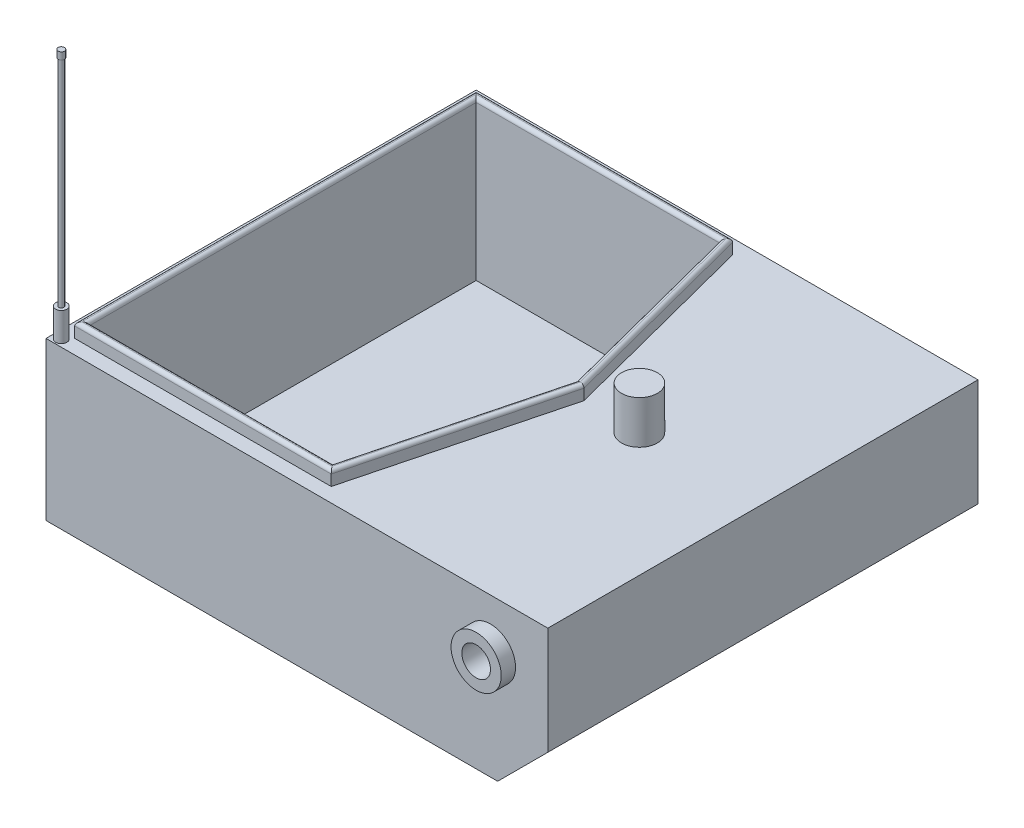
SolidWorks part; units mm, degrees
ref_plane "Front Plane" through (0, 0, 0) normal (0, 0, 1) x (1, 0, 0)
ref_plane "Top Plane" through (0, 0, 0) normal (0, 1, 0) x (1, 0, 0)
ref_plane "Right Plane" through (0, 0, 0) normal (1, 0, 0) x (0, 0, -1)
sketch "Sketch1" plane through (0, 0, 0) normal (0, 0, 1) x (1, 0, 0)
  line L0 (280, -110) -> (350, -40)
  line L1 (-350, -110) -> (280, -110)
  line L2 (-350, -110) -> (-350, 110)
  line L3 (-350, 110) -> (350, 110)
  line L4 (350, -40) -> (350, 110)
  line L5 (-350, -110) -> (350, 110) construction
  line L6 (-350, 110) -> (350, -110) construction
  point P0 (0, 0)
  dimension "D1" = 700
  dimension "D2" = 220
extrude "Boss-Extrude1" add sketch "Sketch1" along normal blind 600
sketch "Sketch2" plane through (0, 110, 0) normal (0, 1, 0) x (1, 0, 0)
  line L0 (20.0986, -30) -> (90.0986, -300)
  line L1 (-320, -30) -> (20.0986, -30)
  line L2 (-320, -30) -> (-320, -570)
  line L3 (-320, -570) -> (20.0986, -570)
  line L5 (90.0986, -300) -> (20.0986, -570)
  line L6 (350, 0) -> (-350, 0) construction
  line L7 (350, -600) -> (-350, -600) construction
  line L8 (-350, -600) -> (-350, 0) construction
  dimension "D1" = 30
  dimension "D2" = 30
  dimension "D3" = 30
extrude "Cut-Extrude1" cut sketch "Sketch2" against normal blind 200
sketch "Sketch3" plane through (0, 110, 0) normal (0, 1, 0) x (1, 0, 0)
  line L0 (-330, -20) -> (-330, -580)
  line L1 (-330, -580) -> (27.8367, -580)
  line L2 (27.8367, -580) -> (100.4292, -300)
  line L3 (100.4292, -300) -> (27.8367, -20)
  line L4 (27.8367, -20) -> (-330, -20)
  line L5 (-320, -30) -> (-320, -570)
  line L6 (-320, -570) -> (20.0986, -570)
  line L7 (20.0986, -570) -> (90.0986, -300)
  line L8 (90.0986, -300) -> (20.0986, -30)
  line L9 (20.0986, -30) -> (-320, -30)
  line L10 (-320, -30) -> (-320, -570)
  line L11 (-320, -570) -> (20.0986, -570)
  line L12 (20.0986, -570) -> (90.0986, -300)
  line L13 (90.0986, -300) -> (20.0986, -30)
  line L14 (20.0986, -30) -> (-320, -30)
  dimension "D1" = 0
  dimension "D2" = 10
extrude "Boss-Extrude2" add sketch "Sketch3" along normal blind 20
fillet "Fillet1" radius 5 10 edges at (-149.9507, 130, 570) (55.0986, 130, 435) (55.0986, 130, 165) (-149.9507, 130, 30) (-320, 130, 300) (64.133, 130, 160) (64.133, 130, 440) (-151.0817, 130, 580) (-330, 130, 300) (-151.0817, 130, 20)
sketch "Sketch4" plane through (0, 0, 600) normal (0, 0, 1) x (1, 0, 0)
  line L0 (350, 110) -> (-350, 110) construction
  line L1 (350, -40) -> (350, 110) construction
  circle A0 centre (270, 40) radius 35
  dimension "D3" = 70
  dimension "D1" = 70
  dimension "D2" = 80
extrude "Boss-Extrude3" add sketch "Sketch4" along normal blind 20
sketch "Sketch5" plane through (0, 0, 0) normal (0, 0, -1) x (-1, 0, 0)
  line L0 (-350, 110) -> (350, 110) construction
  line L1 (-350, -40) -> (-350, 110) construction
  circle A0 centre (-270, 40) radius 35
  dimension "D1" = 70
  dimension "D2" = 70
  dimension "D3" = 80
extrude "Boss-Extrude4" add sketch "Sketch5" along normal blind 20
sketch "Sketch6" plane through (0, 0, 620) normal (0, 0, 1) x (1, 0, 0)
  circle A0 centre (270, 40) radius 10
  dimension "D1" = 20
extrude "Cut-Extrude2" cut sketch "Sketch6" against normal through all
sketch "Sketch7" plane through (0, 110, 0) normal (0, 1, 0) x (1, 0, 0)
  circle A0 centre (177.7521, -300) radius 25
  dimension "D1" = 50
extrude "Boss-Extrude5" add sketch "Sketch7" along normal blind 60
sketch "Sketch9" plane through (0, 0, 620) normal (0, 0, 1) x (1, 0, 0)
  circle A0 centre (270, 40) radius 20
  dimension "D1" = 40
extrude "Cut-Extrude3" cut sketch "Sketch9" against normal through all
sketch "Sketch10" plane through (0, 110, 0) normal (0, 1, 0) x (1, 0, 0)
  circle A0 centre (-338.5353, -590.1135) radius 7.8413
  point P2 (-338.3437, -589.5389)
  point P3 (0, 0)
  point P4 (-338.5353, -590.1135)
extrude "Boss-Extrude6" add sketch "Sketch10" along normal blind 40
sketch "Sketch11" plane through (0, 150, 0) normal (0, 1, 0) x (1, 0, 0)
  circle A0 centre (-338.5353, -590.1135) radius 3.5
  dimension "D1" = 7
extrude "Boss-Extrude7" add sketch "Sketch11" along normal blind 300
sketch "Sketch12" plane through (0, 450, 0) normal (0, 1, 0) x (1, 0, 0)
  circle A0 centre (-338.5353, -590.1135) radius 4.4276
extrude "Boss-Extrude8" add sketch "Sketch12" along normal blind 10
